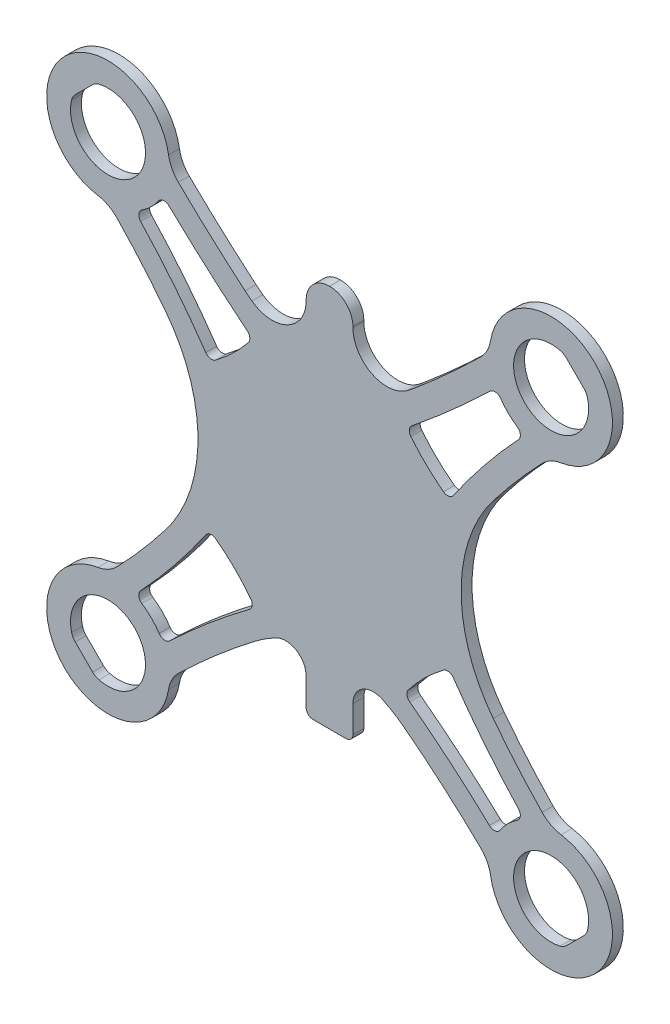
SolidWorks part; units mm, degrees
ref_plane "Front Plane" through (0, 0, 0) normal (0, 0, 1) x (1, 0, 0)
ref_plane "Top Plane" through (0, 0, 0) normal (0, 1, 0) x (1, 0, 0)
ref_plane "Right Plane" through (0, 0, 0) normal (1, 0, 0) x (0, 0, -1)
sketch "Sketch1" plane through (0, 0, 0) normal (0, 0, 1) x (1, 0, 0)
  line L0 (-32.5, 32.5) -> (32.5, -32.5) construction
  line L1 (-32.5, -32.5) -> (32.5, 32.5) construction
  line L2 (-32.5, -23.5) -> (-23.5, -32.5) construction
  line L3 (-19.304, 17.78) -> (19.304, 17.78) construction
  line L4 (-19.304, 17.78) -> (-19.304, -17.78) construction
  line L5 (-19.304, -17.78) -> (19.304, -17.78) construction
  line L6 (19.304, 17.78) -> (19.304, -17.78) construction
  line L7 (32.5, -23.5) -> (23.5, -32.5) construction
  line L8 (23.5, 32.5) -> (32.5, 23.5) construction
  line L9 (-32.5, 23.5) -> (-23.5, 32.5) construction
  line L10 (0, 17.78) -> (0, -17.78) construction
  line L11 (-19.304, 0) -> (19.304, 0) construction
  line L12 (-3.429, -22.1694) -> (-3.429, -26.178)
  line L13 (-2.429, -27.178) -> (2.429, -27.178)
  line L14 (3.429, -26.178) -> (3.429, -22.2297)
  line L15 (-3.429, 25.5442) -> (-3.429, 25.6764)
  line L16 (3.429, 25.6764) -> (3.429, 25.5442)
  line L17 (-0.0254, 29.08) -> (0.0254, 29.08)
  line L18 (-23.5, -32.5) -> (32.5, 23.5) construction
  line L19 (32.5, -23.5) -> (-23.5, 32.5) construction
  line L20 (-32.5, -23.5) -> (23.5, 32.5) construction
  line L21 (-32.5, 23.5) -> (23.5, -32.5) construction
  line L22 (-34.7608, -37.3103) -> (-37.3103, -34.7608)
  line L23 (34.7608, -37.3103) -> (37.3103, -34.7608)
  line L24 (-34.7608, 37.3103) -> (-37.3103, 34.7608)
  line L25 (34.7608, 37.3103) -> (37.3103, 34.7608)
  circle A0 centre (-32.5, -32.5) radius 30 construction
  circle A1 centre (32.5, -32.5) radius 30 construction
  circle A2 centre (32.5, 32.5) radius 30 construction
  circle A3 centre (-32.5, 32.5) radius 30 construction
  circle A4 centre (-32.5, -32.5) radius 5.5 construction
  circle A5 centre (32.5, -32.5) radius 5.5 construction
  circle A6 centre (32.5, 32.5) radius 5.5 construction
  circle A7 centre (-32.5, 32.5) radius 5.5 construction
  circle A8 centre (-32.5, -32.5) radius 9 construction
  circle A9 centre (32.5, -32.5) radius 9 construction
  circle A10 centre (32.5, 32.5) radius 9 construction
  circle A11 centre (-32.5, 32.5) radius 9 construction
  arc A12 (-12.3874, 22.3003) -> (-11.39, 21.5153) centre (0, 37.0135) ccw
  arc A13 (12.3874, 22.3003) -> (11.39, 21.5153) centre (0, 37.0135) cw
  arc A14 (2.429, -27.178) -> (3.429, -26.178) centre (2.429, -26.178) ccw
  arc A15 (-3.429, -26.178) -> (-2.429, -27.178) centre (-2.429, -26.178) ccw
  arc A16 (-10.9379, -21.4895) -> (10.9379, -21.4895) centre (0, -35.7605) cw construction
  arc A17 (-22.1695, -31.1889) -> (-10.9379, -21.4895) centre (66.4181, -122.4181) cw
  arc A18 (10.9379, -21.4895) -> (22.1695, -31.1889) centre (-66.4181, -122.4181) cw
  arc A19 (-12.3874, 22.3003) -> (12.3874, 22.3003) centre (0, 37.0135) ccw construction
  arc A20 (3.429, 25.6764) -> (0.0254, 29.08) centre (0.0254, 25.6764) ccw
  arc A21 (-3.429, 25.6764) -> (-0.0254, 29.08) centre (-0.0254, 25.6764) cw
  arc A22 (-22.1834, 31.1971) -> (-12.3874, 22.3003) centre (101.1226, 157.1226) ccw
  arc A23 (12.3874, 22.3003) -> (22.1834, 31.1971) centre (-101.1226, 157.1226) ccw
  arc A24 (-10.9379, -21.4895) -> (-7.8035, -19.5028) centre (1.7597, -38.0565) cw
  arc A25 (7.7165, -19.52) -> (10.9379, -21.4895) centre (0, -35.7605) cw
  arc A26 (3.429, 25.5442) -> (11.39, 21.5153) centre (8.429, 25.5442) ccw
  arc A27 (-3.429, 25.5442) -> (-11.39, 21.5153) centre (-8.429, 25.5442) cw
  arc A28 (7.7165, -19.52) -> (3.429, -22.2297) centre (6.429, -22.2297) ccw
  arc A29 (-7.8035, -19.5028) -> (-3.429, -22.1694) centre (-6.429, -22.1694) cw
  arc A30 (-31.1803, -22.155) -> (-23.9992, -13.8141) centre (-102.5742, 46.5742) ccw
  arc A31 (-23.9992, -13.8141) -> (-19.304, 0) centre (-41.9736, 0) ccw
  circle A32 centre (-32.5, -32.5) radius 26.4039 construction
  arc A33 (-19.304, 0) -> (-23.9992, 13.8141) centre (-41.9736, 0) ccw
  arc A34 (-23.4525, -27.7027) -> (-11.7612, -17.844) centre (66.4181, -122.4181) cw
  arc A35 (-16.7108, -11.3371) -> (-11.5639, -16.4112) centre (-32.5, -32.5) cw
  arc A36 (16.7108, -11.3371) -> (11.5639, -16.4112) centre (32.5, -32.5) ccw
  arc A37 (-31.1803, 22.155) -> (-23.9992, 13.8141) centre (-102.5742, -46.5742) cw
  arc A38 (23.4525, -27.7027) -> (11.7612, -17.844) centre (-66.4181, -122.4181) ccw
  arc A39 (-33.9673, -23.6204) -> (-23.6197, -33.9631) centre (-32.5, -32.5) ccw
  arc A40 (-27.5328, -24.9949) -> (-24.9987, -27.5271) centre (-32.5, -32.5) cw
  arc A41 (23.6197, -33.9631) -> (33.9673, -23.6204) centre (32.5, -32.5) ccw
  arc A42 (24.9987, -27.5271) -> (27.5328, -24.9949) centre (32.5, -32.5) cw
  circle A43 centre (-32.5, 32.5) radius 26.4039 construction
  arc A44 (-23.563, 27.5274) -> (-12.075, 17.381) centre (101.1226, 157.1226) ccw
  arc A45 (-16.7108, 11.3371) -> (-11.9227, 15.9548) centre (-32.5, 32.5) ccw
  arc A46 (23.563, 27.5274) -> (12.075, 17.381) centre (-101.1226, 157.1226) cw
  arc A47 (-27.714, -23.4536) -> (-18.155, -11.5751) centre (-102.5742, 46.5742) ccw
  arc A48 (16.7108, 11.3371) -> (11.9227, 15.9548) centre (32.5, 32.5) cw
  arc A49 (31.1803, 22.155) -> (23.9992, 13.8141) centre (102.5742, -46.5742) ccw
  arc A50 (-33.9673, 23.6204) -> (-23.6191, 33.9591) centre (-32.5, 32.5) cw
  arc A51 (-27.5328, 24.9949) -> (-25.1025, 27.3739) centre (-32.5, 32.5) ccw
  arc A52 (23.6191, 33.9591) -> (33.9673, 23.6204) centre (32.5, 32.5) cw
  arc A53 (25.1025, 27.3739) -> (27.5328, 24.9949) centre (32.5, 32.5) ccw
  arc A54 (19.304, 0) -> (23.9992, 13.8141) centre (41.9736, 0) cw
  arc A55 (27.714, -23.4536) -> (18.155, -11.5751) centre (102.5742, 46.5742) cw
  arc A56 (23.9992, -13.8141) -> (19.304, 0) centre (41.9736, 0) cw
  arc A57 (31.1803, -22.155) -> (23.9992, -13.8141) centre (102.5742, 46.5742) cw
  arc A58 (23.6197, -33.9631) -> (22.1695, -31.1889) centre (18.6862, -34.7759) ccw
  arc A59 (-27.714, 23.4536) -> (-18.155, 11.5751) centre (-102.5742, -46.5742) cw
  arc A60 (-23.6197, -33.9631) -> (-22.1695, -31.1889) centre (-18.6862, -34.7759) cw
  arc A61 (27.714, 23.4536) -> (18.155, 11.5751) centre (102.5742, -46.5742) ccw
  arc A62 (-18.155, -11.5751) -> (-16.7108, -11.3371) centre (-17.3183, -12.1514) cw
  arc A63 (-11.9227, 15.9548) -> (-12.075, 17.381) centre (-12.7145, 16.5915) ccw
  arc A64 (-25.1025, 27.3739) -> (-23.563, 27.5274) centre (-24.2674, 26.7952) cw
  arc A65 (-27.714, -23.4536) -> (-27.5328, -24.9949) centre (-26.972, -24.1477) ccw
  arc A66 (18.155, -11.5751) -> (16.7108, -11.3371) centre (17.3183, -12.1514) ccw
  arc A67 (23.563, 27.5274) -> (25.1025, 27.3739) centre (24.2674, 26.7952) cw
  arc A68 (11.5639, -16.4112) -> (11.7612, -17.844) centre (12.3695, -17.0303) ccw
  arc A69 (27.714, -23.4536) -> (27.5328, -24.9949) centre (26.972, -24.1477) cw
  arc A70 (27.714, 23.4536) -> (27.5328, 24.9949) centre (26.972, 24.1477) ccw
  arc A71 (23.4525, -27.7027) -> (24.9987, -27.5271) centre (24.1519, -26.9657) ccw
  arc A72 (18.155, 11.5751) -> (16.7108, 11.3371) centre (17.3183, 12.1514) cw
  arc A73 (-11.5639, -16.4112) -> (-11.7612, -17.844) centre (-12.3695, -17.0303) cw
  arc A74 (-18.155, 11.5751) -> (-16.7108, 11.3371) centre (-17.3183, 12.1514) ccw
  arc A75 (-23.4525, -27.7027) -> (-24.9987, -27.5271) centre (-24.1519, -26.9657) cw
  arc A76 (-27.714, 23.4536) -> (-27.5328, 24.9949) centre (-26.972, 24.1477) cw
  arc A77 (12.075, 17.381) -> (11.9227, 15.9548) centre (12.7145, 16.5915) ccw
  arc A78 (-31.1803, 22.155) -> (-33.9673, 23.6204) centre (-34.7824, 18.6873) ccw
  arc A79 (-23.6191, 33.9591) -> (-22.1834, 31.1971) centre (-18.6852, 34.7696) ccw
  arc A80 (33.9673, 23.6204) -> (31.1803, 22.155) centre (34.7824, 18.6873) ccw
  arc A81 (33.9673, -23.6204) -> (31.1803, -22.155) centre (34.7824, -18.6873) cw
  arc A82 (-33.9673, -23.6204) -> (-31.1803, -22.155) centre (-34.7824, -18.6873) ccw
  arc A83 (23.6191, 33.9591) -> (22.1834, 31.1971) centre (18.6852, 34.7696) cw
  arc A84 (-37.8367, -33.8303) -> (-33.8303, -37.8367) centre (-32.5, -32.5) cw
  arc A85 (-34.7608, -37.3103) -> (-33.8303, -37.8367) centre (-33.3466, -35.8961) ccw
  arc A86 (-37.3103, -34.7608) -> (-37.8367, -33.8303) centre (-35.8961, -33.3466) cw
  arc A87 (37.3103, -34.7608) -> (37.8367, -33.8303) centre (35.8961, -33.3466) ccw
  arc A88 (34.7608, -37.3103) -> (33.8303, -37.8367) centre (33.3466, -35.8961) cw
  arc A89 (37.8367, -33.8303) -> (33.8303, -37.8367) centre (32.5, -32.5) ccw
  arc A90 (-34.7608, 37.3103) -> (-33.8303, 37.8367) centre (-33.3466, 35.8961) cw
  arc A91 (-37.8367, 33.8303) -> (-33.8303, 37.8367) centre (-32.5, 32.5) ccw
  arc A92 (-37.3103, 34.7608) -> (-37.8367, 33.8303) centre (-35.8961, 33.3466) ccw
  arc A93 (37.3103, 34.7608) -> (37.8367, 33.8303) centre (35.8961, 33.3466) cw
  arc A94 (34.7608, 37.3103) -> (33.8303, 37.8367) centre (33.3466, 35.8961) ccw
  arc A95 (37.8367, 33.8303) -> (33.8303, 37.8367) centre (32.5, 32.5) cw
  point P5 (0, 0)
  point P19 (0, 17.78)
  point P20 (0, -17.78)
  point P21 (-19.304, 0)
  point P22 (19.304, 0)
  point P35 (-13.8296, -13.8296)
  point P45 (0, -27.178)
  point P46 (3.429, -18.11)
  point P50 (0, 29.08)
  point P53 (3.429, -27.178)
  point P56 (-3.429, -27.178)
  point P57 (0, 17.78)
  point P60 (0, -17.78)
  point P74 (3.429, 29.08)
  point P77 (-3.429, 29.08)
  point P105 (3.429, 18.0881)
  point P114 (-17.5727, -10.7205)
  point P117 (-28.6, -24.3889)
  point P131 (-3.429, 18.0881)
  point P134 (-18.1805, 10.3162)
  point P137 (-11.3018, 16.7582)
  point P140 (-24.48, 28.4159)
  point P141 (17.5727, -10.7205)
  point P143 (-28.6, 24.3889)
  point P146 (28.6, 24.3889)
  point P149 (24.48, 28.4159)
  point P152 (10.9504, -17.2428)
  point P153 (28.6, -24.3889)
  point P155 (18.1805, -10.3162)
  point P157 (28.6, 24.3889)
  point P158 (28.6, -24.3889)
  point P161 (24.3889, -28.6)
  point P164 (17.5727, 10.7205)
  point P167 (-10.9504, -17.2428)
  point P168 (-17.5727, 10.7205)
  point P170 (-28.6, -24.3889)
  point P172 (-24.3889, -28.6)
  point P174 (18.1805, 10.3162)
  point P177 (11.3018, 16.7582)
  point P179 (-28.6, 24.3889)
  point P198 (-36.3891, -36.3891)
  point P201 (-34.4153, -37.6557)
  point P204 (-37.6557, -34.4153)
  dimension "D1" = 60
  dimension "D2" = 11
  dimension "D5" = 18
  dimension "D6" = 11.3
  dimension "D7" = 9.398
  dimension "D8" = 3
  dimension "D11" = 6.858
  dimension "D12" = 5
  dimension "D13" = 3.4036
  dimension "D14" = 1
  dimension "D15" = 1
  dimension "D16" = 3.4036
  dimension "D9" = 3
  dimension "D17" = 1.016
  dimension "D23" = 1.016
  dimension "D24" = 5
  dimension "D25" = 0.5
  dimension "D26" = 2
  dimension "D27" = 5
  dimension "D29" = 5
  dimension "D32" = 1.016
  dimension "D33" = 1.016
  dimension "D36" = 1.016
  dimension "D37" = 1.016
  dimension "D40" = 1.016
  dimension "D42" = 1.016
  dimension "D44" = 1.016
  dimension "D46" = 1.016
  dimension "D3" = 19.304
  dimension "D4" = 17.78
  dimension "D10" = 6.858
  dimension "D18" = 65
  dimension "D19" = 4
  dimension "D20" = 4
  dimension "D21" = 19.558
  dimension "D22" = 4.2
extrude "Boss-Extrude1" add sketch "Sketch1" along normal blind 1.6 contours A17 A24 A29 L12 A15 L13 A14 L14 A28 A25 A18 A58 A41 A81 A57 A56 A54 A49 A80 A52 A83 A23 A13 A26 L16 A20 L17 A21 L15 A27 A12 A22 A79 A50 A78 A37 A33 A31 A30 A82 A39 A60
extrude "Cut-Extrude3" cut sketch "Sketch1<5>" along normal through all contours A45 A63 A44 A64 A51 | A46 A77 A48 A69 A53 A67 | A6 | A5 | A38 A71 A42 A36 A68 | A75 A34 A73 A35 A72 A40 | A4 | A7 | A7 | L22 A86 A84 A85 | L23 A87 A89 A88 | L25 A93 A95 A94 | L24 A92 A91 A90 region at (-19.6446, -19.5292, 0) region at (19.6446, -19.5292, 0) region at (-19.799, 19.431, 0) region at (19.799, 19.431, 0)
sketch "Sketch1<5>" plane through (0, 0, 0) normal (0, 0, 1) x (1, 0, 0) same geometry as "Sketch1"
